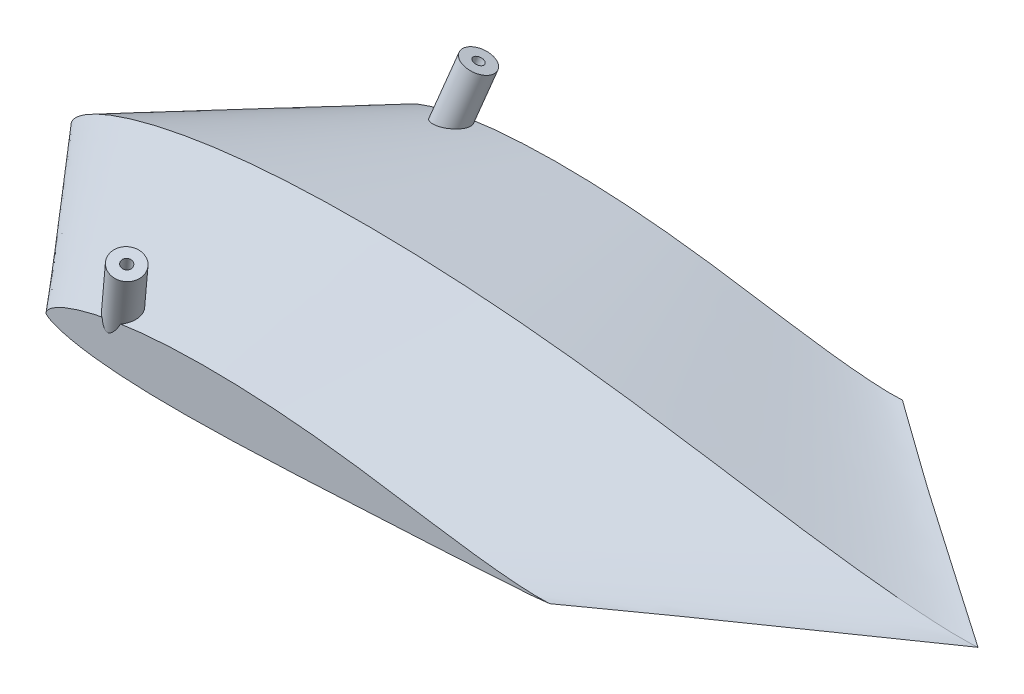
SolidWorks part; units mm, degrees
ref_plane "Front Plane" through (0, 0, 0) normal (0, 0, 1) x (1, 0, 0)
ref_plane "Top Plane" through (0, 0, 0) normal (0, 1, 0) x (1, 0, 0)
ref_plane "Right Plane" through (0, 0, 0) normal (1, 0, 0) x (0, 0, -1)
curve "Curve1"
  spline degree 3 poles (178.8235, -0.1536, 0) (180.3162, 0.0326, 0) (178.6769, -0.0979, 0) (177.3268, -0.1109, 0) (173.9976, -0.1057, 0) (169.9397, 0.1046, 0) (164.6882, 0.4858, 0) (158.5901, 1.1026, 0) (151.6988, 1.9482, 0) (144.1808, 2.9934, 0) (136.1635, 4.1927, 0) (127.7797, 5.4908, 0) (119.1442, 6.8173, 0) (110.3463, 8.0754, 0) (101.4587, 9.2, 0) (92.5465, 10.1562, 0) (83.6758, 10.9156, 0) (74.9166, 11.4682, 0) (66.342, 11.806, 0) (58.028, 11.9274, 0) (50.0487, 11.8319, 0) (42.4741, 11.515, 0) (35.367, 10.9819, 0) (28.7822, 10.24, 0) (22.7701, 9.3088, 0) (17.3773, 8.2269, 0) (12.6499, 7.0268, 0) (8.6305, 5.74, 0) (5.3502, 4.4039, 0) (2.8359, 3.0632, 0) (1.2518, 1.9009, 0) (0.4818, 1.0554, 0) (0.1891, 0.6046, 0) (0.0579, 0.3158, 0) (-0.0016, 0.0856, 0) (-0.0042, -0.0985, 0) (0.0738, -0.2696, 0) (0.2282, -0.4702, 0) (0.4808, -0.7088, 0) (0.9335, -1.0446, 0) (2.0075, -1.6855, 0) (4.0408, -2.5002, 0) (7.1529, -3.4084, 0) (11.097, -4.2605, 0) (15.8307, -5.0186, 0) (21.3187, -5.6503, 0) (27.5191, -6.1332, 0) (34.3853, -6.4628, 0) (41.8623, -6.6344, 0) (49.8874, -6.6565, 0) (58.3886, -6.5391, 0) (67.2847, -6.306, 0) (76.4836, -5.9763, 0) (85.8843, -5.5795, 0) (95.3777, -5.1338, 0) (104.8501, -4.6614, 0) (114.1865, -4.1746, 0) (123.2728, -3.6881, 0) (131.998, -3.2085, 0) (140.2557, -2.7461, 0) (147.9458, -2.3044, 0) (154.9716, -1.8945, 0) (161.2526, -1.5152, 0) (166.6878, -1.1747, 0) (171.2749, -0.8603, 0) (174.7811, -0.5984, 0) (177.6251, -0.3216, 0) (178.8235, -0.1536, 0) (180.3162, 0.0326, 0) (178.6769, -0.0979, 0) knots -0.013312 -0.00609 -0.00158 0 0.001669 0.006747 0.015187 0.026742 0.041155 0.058129 0.077283 0.098227 0.12058 0.143966 0.168018 0.192451 0.217075 0.24171 0.266182 0.29031 0.313903 0.336767 0.358704 0.37954 0.399122 0.417322 0.434037 0.449154 0.462553 0.474139 0.483848 0.491647 0.497539 0.499898 0.501005 0.501951 0.502492 0.502956 0.503431 0.504004 0.505035 0.506276 0.508636 0.515301 0.524213 0.535296 0.548467 0.563638 0.580726 0.599619 0.62018 0.642246 0.665633 0.690118 0.715452 0.741354 0.76752 0.793634 0.819375 0.844429 0.868488 0.891259 0.912467 0.93185 0.949165 0.964196 0.976755 0.986688 0.99391 0.99842 1 1.001669 1.006747 1.015187 periodic
ref_plane "Plane1" through (0, 0, -35) normal (0, 0, 1) x (1, 0, 0)
sketch "Sketch2" plane through (0, 0, 0) normal (0, 0, 1) x (1, 0, 0)
  line L0 (180, 0) -> (0, 0) construction
  spline S0 degree 3 poles (178.8235, -0.1536) (180.3162, 0.0326) (178.6769, -0.0979) (177.3268, -0.1109) (173.9976, -0.1057) (169.9397, 0.1046) (164.6882, 0.4858) (158.5901, 1.1026) (151.6988, 1.9482) (144.1808, 2.9934) (136.1635, 4.1927) (127.7797, 5.4908) (119.1442, 6.8173) (110.3463, 8.0754) (101.4587, 9.2) (92.5465, 10.1562) (83.6758, 10.9156) (74.9166, 11.4682) (66.342, 11.806) (58.028, 11.9274) (50.0487, 11.8319) (42.4741, 11.515) (35.367, 10.9819) (28.7822, 10.24) (22.7701, 9.3088) (17.3773, 8.2269) (12.6499, 7.0268) (8.6305, 5.74) (5.3502, 4.4039) (2.8359, 3.0632) (1.2518, 1.9009) (0.4818, 1.0554) (0.1891, 0.6046) (0.0579, 0.3158) (-0.0016, 0.0856) (-0.0042, -0.0985) (0.0738, -0.2696) (0.2282, -0.4702) (0.4808, -0.7088) (0.9335, -1.0446) (2.0075, -1.6855) (4.0408, -2.5002) (7.1529, -3.4084) (11.097, -4.2605) (15.8307, -5.0186) (21.3187, -5.6503) (27.5191, -6.1332) (34.3853, -6.4628) (41.8623, -6.6344) (49.8874, -6.6565) (58.3886, -6.5391) (67.2847, -6.306) (76.4836, -5.9763) (85.8843, -5.5795) (95.3777, -5.1338) (104.8501, -4.6614) (114.1865, -4.1746) (123.2728, -3.6881) (131.998, -3.2085) (140.2557, -2.7461) (147.9458, -2.3044) (154.9716, -1.8945) (161.2526, -1.5152) (166.6878, -1.1747) (171.2749, -0.8603) (174.7811, -0.5984) (177.6251, -0.3216) (178.8235, -0.1536) (180.3162, 0.0326) (178.6769, -0.0979) knots -0.013312 -0.00609 -0.00158 0 0.001669 0.006747 0.015187 0.026742 0.041155 0.058129 0.077283 0.098227 0.12058 0.143966 0.168018 0.192451 0.217075 0.24171 0.266182 0.29031 0.313903 0.336767 0.358704 0.37954 0.399122 0.417322 0.434037 0.449154 0.462553 0.474139 0.483848 0.491647 0.497539 0.499898 0.501005 0.501951 0.502492 0.502956 0.503431 0.504004 0.505035 0.506276 0.508636 0.515301 0.524213 0.535296 0.548467 0.563638 0.580726 0.599619 0.62018 0.642246 0.665633 0.690118 0.715452 0.741354 0.76752 0.793634 0.819375 0.844429 0.868488 0.891259 0.912467 0.93185 0.949165 0.964196 0.976755 0.986688 0.99391 0.99842 1 1.001669 1.006747 1.015187 only from (180, 0) to (180, 0) construction
  spline S1 degree 3 poles (178.8235, -0.1536) (180.3162, 0.0326) (178.6769, -0.0979) (177.3268, -0.1109) (173.9976, -0.1057) (169.9397, 0.1046) (164.6882, 0.4858) (158.5901, 1.1026) (151.6988, 1.9482) (144.1808, 2.9934) (136.1635, 4.1927) (127.7797, 5.4908) (119.1442, 6.8173) (110.3463, 8.0754) (101.4587, 9.2) (92.5465, 10.1562) (83.6758, 10.9156) (74.9166, 11.4682) (66.342, 11.806) (58.028, 11.9274) (50.0487, 11.8319) (42.4741, 11.515) (35.367, 10.9819) (28.7822, 10.24) (22.7701, 9.3088) (17.3773, 8.2269) (12.6499, 7.0268) (8.6305, 5.74) (5.3502, 4.4039) (2.8359, 3.0632) (1.2518, 1.9009) (0.4818, 1.0554) (0.1891, 0.6046) (0.0579, 0.3158) (-0.0016, 0.0856) (-0.0042, -0.0985) (0.0738, -0.2696) (0.2282, -0.4702) (0.4808, -0.7088) (0.9335, -1.0446) (2.0075, -1.6855) (4.0408, -2.5002) (7.1529, -3.4084) (11.097, -4.2605) (15.8307, -5.0186) (21.3187, -5.6503) (27.5191, -6.1332) (34.3853, -6.4628) (41.8623, -6.6344) (49.8874, -6.6565) (58.3886, -6.5391) (67.2847, -6.306) (76.4836, -5.9763) (85.8843, -5.5795) (95.3777, -5.1338) (104.8501, -4.6614) (114.1865, -4.1746) (123.2728, -3.6881) (131.998, -3.2085) (140.2557, -2.7461) (147.9458, -2.3044) (154.9716, -1.8945) (161.2526, -1.5152) (166.6878, -1.1747) (171.2749, -0.8603) (174.7811, -0.5984) (177.6251, -0.3216) (178.8235, -0.1536) (180.3162, 0.0326) (178.6769, -0.0979) knots -0.013312 -0.00609 -0.00158 0 0.001669 0.006747 0.015187 0.026742 0.041155 0.058129 0.077283 0.098227 0.12058 0.143966 0.168018 0.192451 0.217075 0.24171 0.266182 0.29031 0.313903 0.336767 0.358704 0.37954 0.399122 0.417322 0.434037 0.449154 0.462553 0.474139 0.483848 0.491647 0.497539 0.499898 0.501005 0.501951 0.502492 0.502956 0.503431 0.504004 0.505035 0.506276 0.508636 0.515301 0.524213 0.535296 0.548467 0.563638 0.580726 0.599619 0.62018 0.642246 0.665633 0.690118 0.715452 0.741354 0.76752 0.793634 0.819375 0.844429 0.868488 0.891259 0.912467 0.93185 0.949165 0.964196 0.976755 0.986688 0.99391 0.99842 1 1.001669 1.006747 1.015187 only from (180, 0) to (180, 0)
  point P4 (0, 0)
curve "Curve2"
  spline degree 3 poles (129.3464, -0.0853, 0) (130.1757, 0.0181, 0) (129.2649, -0.0544, 0) (128.5149, -0.0616, 0) (126.6653, -0.0587, 0) (124.4109, 0.0581, 0) (121.4935, 0.2699, 0) (118.1056, 0.6125, 0) (114.2771, 1.0823, 0) (110.1004, 1.663, 0) (105.6464, 2.3293, 0) (100.9887, 3.0504, 0) (96.1912, 3.7874, 0) (91.3035, 4.4863, 0) (86.366, 5.1111, 0) (81.4147, 5.6423, 0) (76.4865, 6.0642, 0) (71.6203, 6.3712, 0) (66.8567, 6.5589, 0) (62.2378, 6.6263, 0) (57.8048, 6.5733, 0) (53.5967, 6.3972, 0) (49.6483, 6.1011, 0) (45.9901, 5.6889, 0) (42.65, 5.1716, 0) (39.654, 4.5705, 0) (37.0277, 3.9038, 0) (34.7947, 3.1889, 0) (32.9723, 2.4466, 0) (31.5755, 1.7018, 0) (30.6954, 1.0561, 0) (30.2677, 0.5864, 0) (30.1051, 0.3359, 0) (30.0322, 0.1755, 0) (29.9991, 0.0476, 0) (29.9977, -0.0547, 0) (30.041, -0.1498, 0) (30.1268, -0.2612, 0) (30.2671, -0.3938, 0) (30.5186, -0.5803, 0) (31.1153, -0.9364, 0) (32.2449, -1.389, 0) (33.9738, -1.8935, 0) (36.165, -2.3669, 0) (38.7949, -2.7881, 0) (41.8437, -3.1391, 0) (45.2884, -3.4073, 0) (49.1029, -3.5905, 0) (53.2568, -3.6858, 0) (57.7152, -3.6981, 0) (62.4381, -3.6328, 0) (67.3804, -3.5033, 0) (72.4909, -3.3202, 0) (77.7135, -3.0997, 0) (82.9876, -2.8521, 0) (88.2501, -2.5897, 0) (93.437, -2.3192, 0) (98.4849, -2.0489, 0) (103.3322, -1.7825, 0) (107.9198, -1.5256, 0) (112.1921, -1.2802, 0) (116.0954, -1.0525, 0) (119.5848, -0.8418, 0) (122.6043, -0.6526, 0) (125.1527, -0.4779, 0) (127.1006, -0.3325, 0) (128.6806, -0.1786, 0) (129.3464, -0.0853, 0) (130.1757, 0.0181, 0) (129.2649, -0.0544, 0) knots -0.013312 -0.00609 -0.00158 0 0.001669 0.006747 0.015187 0.026742 0.041155 0.058129 0.077283 0.098227 0.12058 0.143966 0.168018 0.192451 0.217075 0.24171 0.266182 0.29031 0.313903 0.336767 0.358704 0.37954 0.399122 0.417322 0.434037 0.449154 0.462553 0.474139 0.483848 0.491647 0.497539 0.499898 0.501005 0.501951 0.502492 0.502956 0.503431 0.504004 0.505035 0.506276 0.508636 0.515301 0.524213 0.535296 0.548467 0.563638 0.580726 0.599619 0.62018 0.642246 0.665633 0.690118 0.715452 0.741354 0.76752 0.793634 0.819375 0.844429 0.868488 0.891259 0.912467 0.93185 0.949165 0.964196 0.976755 0.986688 0.99391 0.99842 1 1.001669 1.006747 1.015187 periodic
sketch "Sketch3" plane through (0, 0, -35) normal (0, 0, 1) x (1, 0, 0)
  line L0 (130, 0) -> (29.9996, 0) construction
  spline S0 degree 3 poles (129.3464, -0.0853) (130.1757, 0.0181) (129.2649, -0.0544) (128.5149, -0.0616) (126.6653, -0.0587) (124.4109, 0.0581) (121.4935, 0.2699) (118.1056, 0.6125) (114.2771, 1.0823) (110.1004, 1.663) (105.6464, 2.3293) (100.9887, 3.0504) (96.1912, 3.7874) (91.3035, 4.4863) (86.366, 5.1111) (81.4147, 5.6423) (76.4865, 6.0642) (71.6203, 6.3712) (66.8567, 6.5589) (62.2378, 6.6263) (57.8048, 6.5733) (53.5967, 6.3972) (49.6483, 6.1011) (45.9901, 5.6889) (42.65, 5.1716) (39.654, 4.5705) (37.0277, 3.9038) (34.7947, 3.1889) (32.9723, 2.4466) (31.5755, 1.7018) (30.6954, 1.0561) (30.2677, 0.5864) (30.1051, 0.3359) (30.0322, 0.1755) (29.9991, 0.0476) (29.9977, -0.0547) (30.041, -0.1498) (30.1268, -0.2612) (30.2671, -0.3938) (30.5186, -0.5803) (31.1153, -0.9364) (32.2449, -1.389) (33.9738, -1.8935) (36.165, -2.3669) (38.7949, -2.7881) (41.8437, -3.1391) (45.2884, -3.4073) (49.1029, -3.5905) (53.2568, -3.6858) (57.7152, -3.6981) (62.4381, -3.6328) (67.3804, -3.5033) (72.4909, -3.3202) (77.7135, -3.0997) (82.9876, -2.8521) (88.2501, -2.5897) (93.437, -2.3192) (98.4849, -2.0489) (103.3322, -1.7825) (107.9198, -1.5256) (112.1921, -1.2802) (116.0954, -1.0525) (119.5848, -0.8418) (122.6043, -0.6526) (125.1527, -0.4779) (127.1006, -0.3325) (128.6806, -0.1786) (129.3464, -0.0853) (130.1757, 0.0181) (129.2649, -0.0544) knots -0.013312 -0.00609 -0.00158 0 0.001669 0.006747 0.015187 0.026742 0.041155 0.058129 0.077283 0.098227 0.12058 0.143966 0.168018 0.192451 0.217075 0.24171 0.266182 0.29031 0.313903 0.336767 0.358704 0.37954 0.399122 0.417322 0.434037 0.449154 0.462553 0.474139 0.483848 0.491647 0.497539 0.499898 0.501005 0.501951 0.502492 0.502956 0.503431 0.504004 0.505035 0.506276 0.508636 0.515301 0.524213 0.535296 0.548467 0.563638 0.580726 0.599619 0.62018 0.642246 0.665633 0.690118 0.715452 0.741354 0.76752 0.793634 0.819375 0.844429 0.868488 0.891259 0.912467 0.93185 0.949165 0.964196 0.976755 0.986688 0.99391 0.99842 1 1.001669 1.006747 1.015187 only from (130, 0) to (130, 0) construction
  spline S1 degree 3 poles (129.3464, -0.0853) (130.1757, 0.0181) (129.2649, -0.0544) (128.5149, -0.0616) (126.6653, -0.0587) (124.4109, 0.0581) (121.4935, 0.2699) (118.1056, 0.6125) (114.2771, 1.0823) (110.1004, 1.663) (105.6464, 2.3293) (100.9887, 3.0504) (96.1912, 3.7874) (91.3035, 4.4863) (86.366, 5.1111) (81.4147, 5.6423) (76.4865, 6.0642) (71.6203, 6.3712) (66.8567, 6.5589) (62.2378, 6.6263) (57.8048, 6.5733) (53.5967, 6.3972) (49.6483, 6.1011) (45.9901, 5.6889) (42.65, 5.1716) (39.654, 4.5705) (37.0277, 3.9038) (34.7947, 3.1889) (32.9723, 2.4466) (31.5755, 1.7018) (30.6954, 1.0561) (30.2677, 0.5864) (30.1051, 0.3359) (30.0322, 0.1755) (29.9991, 0.0476) (29.9977, -0.0547) (30.041, -0.1498) (30.1268, -0.2612) (30.2671, -0.3938) (30.5186, -0.5803) (31.1153, -0.9364) (32.2449, -1.389) (33.9738, -1.8935) (36.165, -2.3669) (38.7949, -2.7881) (41.8437, -3.1391) (45.2884, -3.4073) (49.1029, -3.5905) (53.2568, -3.6858) (57.7152, -3.6981) (62.4381, -3.6328) (67.3804, -3.5033) (72.4909, -3.3202) (77.7135, -3.0997) (82.9876, -2.8521) (88.2501, -2.5897) (93.437, -2.3192) (98.4849, -2.0489) (103.3322, -1.7825) (107.9198, -1.5256) (112.1921, -1.2802) (116.0954, -1.0525) (119.5848, -0.8418) (122.6043, -0.6526) (125.1527, -0.4779) (127.1006, -0.3325) (128.6806, -0.1786) (129.3464, -0.0853) (130.1757, 0.0181) (129.2649, -0.0544) knots -0.013312 -0.00609 -0.00158 0 0.001669 0.006747 0.015187 0.026742 0.041155 0.058129 0.077283 0.098227 0.12058 0.143966 0.168018 0.192451 0.217075 0.24171 0.266182 0.29031 0.313903 0.336767 0.358704 0.37954 0.399122 0.417322 0.434037 0.449154 0.462553 0.474139 0.483848 0.491647 0.497539 0.499898 0.501005 0.501951 0.502492 0.502956 0.503431 0.504004 0.505035 0.506276 0.508636 0.515301 0.524213 0.535296 0.548467 0.563638 0.580726 0.599619 0.62018 0.642246 0.665633 0.690118 0.715452 0.741354 0.76752 0.793634 0.819375 0.844429 0.868488 0.891259 0.912467 0.93185 0.949165 0.964196 0.976755 0.986688 0.99391 0.99842 1 1.001669 1.006747 1.015187 only from (130, 0) to (130, 0)
loft "Loft1" add profiles "Sketch2", "Sketch3" connector at (55.3868, 11.8834, 0) connector at (61.3985, 6.6053, -35)
mirror "Mirror1" [suppressed] about plane through (0, 0, 0) normal (0, 0, 1)
ref_axis "Axis4" through (0, 0, -61.6271) along (0, 0, 1)
ref_axis "Axis1" through (180, 0, 0) along (-1, 0, 0)
ref_axis "Axis2" through (130, 0, -35) along (-1, 0, 0)
ref_point "Point1"
ref_axis "Axis3" through (-0.0007, 0, 0) along (0.6508, 0, -0.7593)
sketch "Sketch4" plane through (0, 0, 0) normal (0, 1, 0) x (1, 0, 0)
  line L0 (0, 0) -> (141.8779, 107.8393) construction
  line L1 (0, 0) -> (100, 360) construction
  line L3 (25.3509, 91.2632) -> (60.0348, 45.6316) construction
  line L4 (94.7187, 0) -> (60.0348, 45.6316) construction
  line L5 (180, 0) -> (0, 0) construction
  dimension "D1" = 360
  dimension "D2" = 100
ref_plane "Plane2" through (0, 0, 0) normal (0.6051, 0, 0.7961) x (0.7961, 0, -0.6051)
sketch "Sketch5" plane through (0, 0, 0) normal (0.6051, 0, 0.7961) x (0.7961, 0, -0.6051)
  line L0 (42.0724, -26.6467) -> (64.7445, 35.6444) construction
  line L1 (42.0724, -26.6467) -> (42.0724, 24.9899) construction
  dimension "D1" = 20
ref_axis "RotationAxis" through (33.7471, -25.7769, -25.6507) along (0.2723, 0.9397, -0.207)
ref_point "Point2"
mirror "Mirror2" about plane through (0, 0, 0) normal (0, 0, 1) of bodies 101
sketch "Sketch6" plane through (0, 0, 0) normal (0.6051, 0, 0.7961) x (0.7961, 0, -0.6051)
  line L0 (60.5227, 15.2735) -> (58.6433, 15.9576)
  line L1 (58.6433, 15.9576) -> (53.3137, 1.3145)
  line L2 (53.3137, 1.3145) -> (55.193, 0.6305)
  line L3 (55.193, 0.6305) -> (60.5227, 15.2735)
  line L4 (42.389, -25.7769) -> (65.884, 38.7751) construction
  dimension "D1" = 2
  dimension "D2" = 1
revolve "Revolve1" add sketch "Sketch6" angle 360 about axis through (33.7471, -25.7769, -25.6507) along (0.2723, 0.9397, -0.207)
mirror "Mirror3" about plane through (0, 0, 0) normal (0, 0, 1) of bodies 107
